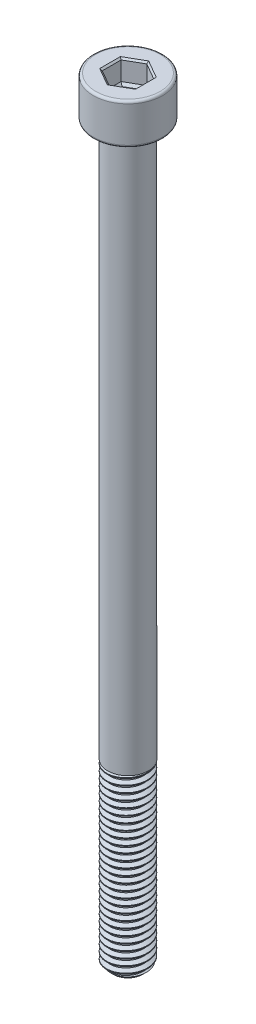
SolidWorks part; units mm, degrees
material "AISI Type A2 Tool Steel"
ref_plane "Front Plane" through (0, 0, 0) normal (0, 0, 1) x (1, 0, 0)
ref_plane "Top Plane" through (0, 0, 0) normal (0, 1, 0) x (1, 0, 0)
ref_plane "Right Plane" through (0, 0, 0) normal (1, 0, 0) x (0, 0, -1)
sketch "Sketch1" plane through (0, 0, 0) normal (0, 1, 0) x (1, 0, 0)
  circle A0 centre (0, 0) radius 2.5
  dimension "D1" = 5
extrude "Boss-Extrude1" add sketch "Sketch1" along normal blind 22
thread "Thread1" pitch 0.8 method cut profile "Thread Profile1" start angle 0, offset 1, length 0, pitch 0.8, diameter 5
ref_plane "Plane1" through (-2.5, 23, 0) normal (0, 0, 1) x (-1, 0, 0)
sketch "Thread Profile1" plane through (-2.5, 23, 0) normal (0, 0, 1) x (-1, 0, 0)
  line L0 (0, 0) -> (0, 0.8) construction
  line L11 (0, 0) -> (0, 0.7)
  line L12 (0, 0.7) -> (-0.433, 0.45)
  line L13 (-0.433, 0.45) -> (-0.433, 0.25)
  line L15 (-0.433, 0.25) -> (0, 0)
  line L17 (-0.433, 0.35) -> (0, 0.35) construction
  point P2 (0, 0)
  dimension "Pitch" = 0.8
  dimension "Profile_Angle" = 60
  dimension "Profile_Land" = 0.2
  dimension "Profile_Height" = 0.433
sketch "Sketch2" plane through (0, 22, 0) normal (0, 1, 0) x (1, 0, 0)
  circle A0 centre (0, 0) radius 2.5
  dimension "D1" = 5
extrude "Boss-Extrude2" add sketch "Sketch2" along normal blind 68
sketch "Sketch3" plane through (0, 90, 0) normal (0, 1, 0) x (1, 0, 0)
  circle A0 centre (0, 0) radius 4.25
  dimension "D1" = 8.5
extrude "Boss-Extrude3" add sketch "Sketch3" along normal blind 5
fillet "Fillet1" radius 0.3 2 edges at (0, 90, 4.25) (0, 95, 4.25)
sketch "Sketch4" plane through (0, 0, 0) normal (0, 0, 1) x (1, 0, 0)
  line L0 (0, 0) -> (0, 0.4416) construction
  line L1 (0, 0) -> (2.51, 0) construction
  line L2 (2.51, 0) -> (2.51, 0.7)
  line L3 (2.51, 0.7) -> (1.81, 0)
  line L4 (1.81, 0) -> (2.51, 0)
  dimension "D1" = 0.7
  dimension "D2" = 45
  dimension "D3" = 2.51
revolve "Cut-Revolve1" cut sketch "Sketch4" angle 360 about L0
sketch "Sketch5" plane through (0, 95, 0) normal (0, 1, 0) x (1, 0, 0)
  line L1 (0, 2.3094) -> (-2, 1.1547)
  line L2 (-2, 1.1547) -> (-2, -1.1547)
  line L3 (-2, -1.1547) -> (0, -2.3094)
  line L4 (0, -2.3094) -> (2, -1.1547)
  line L5 (2, -1.1547) -> (2, 1.1547)
  line L6 (2, 1.1547) -> (0, 2.3094)
  circle A0 centre (0, 0) radius 2 construction
  dimension "D1" = 4
extrude "Cut-Extrude1" cut sketch "Sketch5" against normal blind 2.5
chamfer "Chamfer1" distance 0.2 angle 45 6 edges at (-1, 95, 1.7321) (1, 95, 1.7321) (2, 95, 0) (1, 95, -1.7321) (-1, 95, -1.7321) (-2, 95, 0)
sketch "Sketch6" plane through (0, 92.5, 0) normal (0, 1, 0) x (1, 0, 0)
  line L1 (0, 2.3094) -> (-2, 1.1547)
  line L2 (-2, 1.1547) -> (-2, -1.1547)
  line L3 (-2, -1.1547) -> (0, -2.3094)
  line L4 (0, -2.3094) -> (2, -1.1547)
  line L5 (2, -1.1547) -> (2, 1.1547)
  line L6 (2, 1.1547) -> (0, 2.3094)
  circle A0 centre (0, 0) radius 2 construction
extrude "Cut-Extrude2" cut sketch "Sketch6" against normal blind 0.3 draft 45
